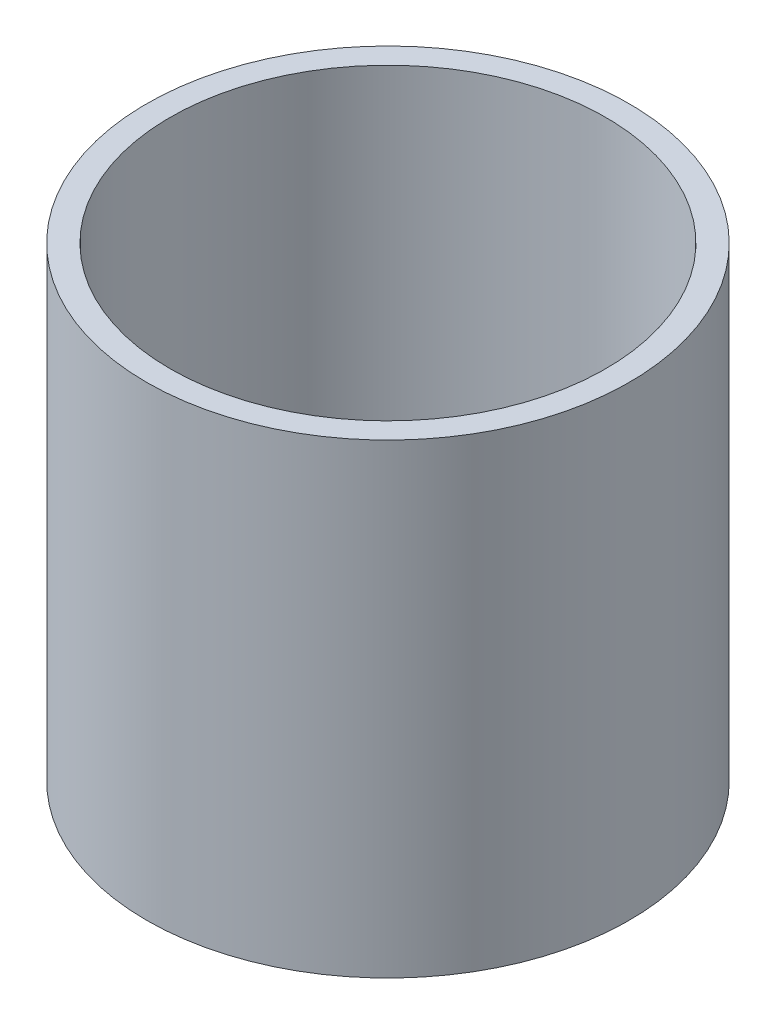
SolidWorks part; units mm, degrees
ref_plane "Front Plane" through (0, 0, 0) normal (0, 0, 1) x (1, 0, 0)
ref_plane "Top Plane" through (0, 0, 0) normal (0, 1, 0) x (1, 0, 0)
ref_plane "Right Plane" through (0, 0, 0) normal (1, 0, 0) x (0, 0, -1)
sketch "Sketch1" plane through (0, 0, 0) normal (0, 1, 0) x (1, 0, 0)
  circle A0 centre (0, 0) radius 42.5
  dimension "SLEEVE_OD" = 85
extrude "Boss-Extrude1" add sketch "Sketch1" along normal blind 82.048
sketch "Sketch2" plane through (0, 0, 0) normal (0, 1, 0) x (1, 0, 0)
  circle A0 centre (0, 0) radius 38.3566
  dimension "BORE_D" = 76.7132
extrude "Cut-Extrude1" cut sketch "Sketch2" along normal through all
chamfer "Chamfer1" distance 3.7292 angle 22.224 rebuild error yes
